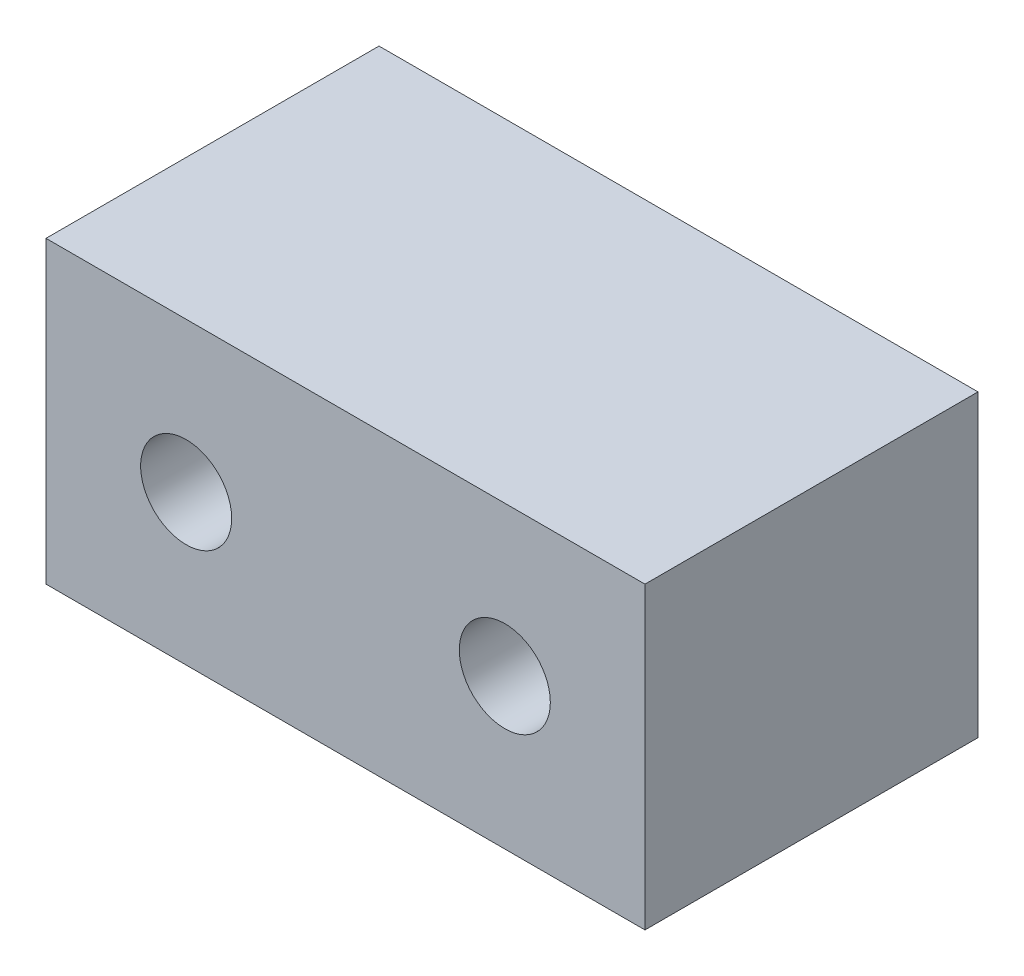
SolidWorks part; units mm, degrees
ref_plane "Front Plane" through (0, 0, 0) normal (0, 0, 1) x (1, 0, 0)
ref_plane "Top Plane" through (0, 0, 0) normal (0, 1, 0) x (1, 0, 0)
ref_plane "Right Plane" through (0, 0, 0) normal (1, 0, 0) x (0, 0, -1)
sketch "Sketch1" plane through (0, 0, 0) normal (0, 0, 1) x (1, 0, 0)
  line L0 (-6.35, 0) -> (6.35, 0) construction
  line L1 (-6.35, -3.175) -> (6.35, -3.175)
  line L2 (-6.35, -3.175) -> (-6.35, 3.175)
  line L3 (-6.35, 3.175) -> (6.35, 3.175)
  line L4 (6.35, -3.175) -> (6.35, 3.175)
  line L5 (-6.35, -3.175) -> (6.35, 3.175) construction
  line L6 (-6.35, 3.175) -> (6.35, -3.175) construction
  line L7 (0, 3.175) -> (0, -3.175) construction
  circle A0 centre (-3.3782, 0) radius 0.9652
  circle A2 centre (3.3782, 0) radius 0.9652
  circle A3 centre (-3.3782, 0) radius 1.9939
  circle A4 centre (3.3782, 0) radius 1.9939
  point P0 (0, 0)
  dimension "D3" = 1.9304
  dimension "D5" = 3.9878
  dimension "D1" = 6.35
  dimension "D2" = 12.7
  dimension "D4" = 3.3782
extrude "Boss-Extrude1" add sketch "Sketch1" along normal blind 7.0612 contours L1 L4 L3 L2 A3 A4 | A3 A0 | A4 A2 region at (0, 0, 0) region at (-5.3157, 0, 0) region at (1.4407, 0, 0)
extrude "Cut-Extrude1" cut sketch "Sketch1<3>" along normal blind 3.556 contours A4 A2 | A3 A0 region at (-5.3157, 0, 0) region at (1.4407, 0, 0)
sketch "Sketch1<3>" plane through (0, 0, 0) normal (0, 0, 1) x (1, 0, 0) same geometry as "Sketch1"
